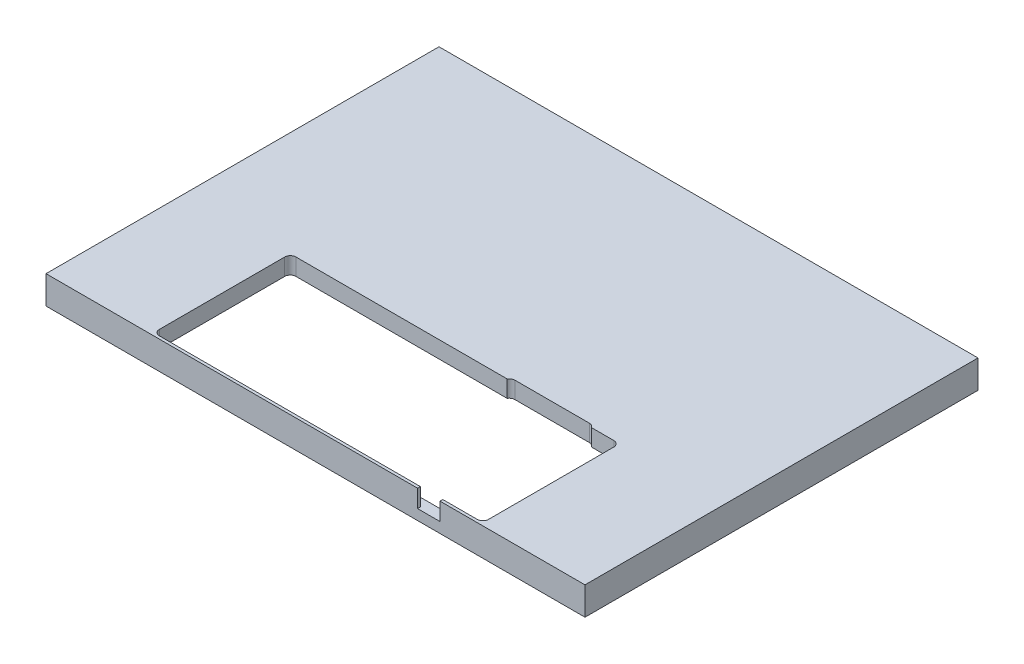
SolidWorks part; units mm, degrees
ref_plane "Front Plane" through (0, 0, 0) normal (0, 0, 1) x (1, 0, 0)
ref_plane "Top Plane" through (0, 0, 0) normal (0, 1, 0) x (1, 0, 0)
ref_plane "Right Plane" through (0, 0, 0) normal (1, 0, 0) x (0, 0, -1)
sketch "Sketch1" plane through (0, 0, 0) normal (0, 1, 0) x (1, 0, 0)
  line L0 (5.08, 5.08) -> (238.76, 5.08)
  line L1 (0, 0) -> (243.84, 0)
  line L2 (0, 0) -> (0, 177.8)
  line L3 (0, 177.8) -> (243.84, 177.8)
  line L4 (243.84, 0) -> (243.84, 177.8)
  line L5 (238.76, 5.08) -> (238.76, 172.72)
  line L6 (5.08, 172.72) -> (238.76, 172.72)
  line L7 (5.08, 5.08) -> (5.08, 172.72)
  dimension "D1" = 177.8
  dimension "D2" = 243.84
  dimension "D3" = 5.08
extrude "Boss-Extrude7" add sketch "Sketch1" along normal blind 12.7
sketch "Sketch6" plane through (0, 12.7, 0) normal (0, 1, 0) x (1, 0, 0)
  line L0 (5.08, 172.72) -> (5.08, 5.08)
  line L1 (5.08, 5.08) -> (238.76, 5.08)
  line L2 (238.76, 5.08) -> (238.76, 172.72)
  line L3 (238.76, 172.72) -> (5.08, 172.72)
extrude "Boss-Extrude8" add sketch "Sketch6" against normal blind 7.62
sketch "Sketch7" plane through (0, 12.7, 0) normal (0, 1, 0) x (1, 0, 0)
  line L0 (0, 0) -> (243.84, 0) construction
  line L1 (0, 177.8) -> (0, 0) construction
  line L2 (243.84, 0) -> (243.84, 177.8) construction
  line L3 (196.37, 1.27) -> (178.2581, 1.27)
  line L4 (47.47, 1.27) -> (47.47, 63.07)
  line L6 (196.37, 63.07) -> (196.37, 1.27)
  line L8 (47.47, 32.17) -> (0, 32.17) construction
  line L9 (196.37, 32.17) -> (243.84, 32.17) construction
  line L11 (168.0981, 0) -> (178.2581, 0)
  line L12 (178.2581, 0) -> (178.2581, 1.27)
  line L14 (157.9954, 1.27) -> (47.47, 1.27)
  line L15 (157.9954, 1.27) -> (168.0981, 1.27)
  line L16 (168.0981, 1.27) -> (168.0981, 0)
  line L18 (183.67, 64.34) -> (145.57, 64.34)
  line L20 (196.37, 63.07) -> (183.67, 63.07)
  line L21 (145.57, 63.07) -> (47.47, 63.07)
  line L22 (183.67, 63.07) -> (183.67, 64.34)
  line L23 (145.57, 63.07) -> (145.57, 64.34)
  dimension "D1" = 1.27
  dimension "D2" = 148.9
  dimension "D3" = 61.8
  dimension "D4" = 10.16
  dimension "D5" = 38.1
  dimension "D6" = 12.7
  dimension "D7" = 1.27
extrude "Cut-Extrude2" cut sketch "Sketch7" against normal blind 8 contours L4 L21 L23 L18 L22 L20 L6 L3 L12 L11 L16 L15 L14
fillet "Fillet1" radius 2.54 4 edges at (47.47, 8.89, -63.07) (47.47, 8.7, -1.27) (196.37, 8.7, -1.27) (196.37, 8.89, -63.07)
fillet "Fillet2" radius 2.54 2 edges at (145.57, 8.89, -64.34) (183.67, 8.89, -64.34)
sketch "Sketch8" plane through (0, 12.7, 0) normal (0, 1, 0) x (1, 0, 0)
  line L0 (50.5293, 86.591) -> (50.5293, 97.9956)
  line L1 (50.5293, 97.9956) -> (62.5181, 97.9956)
  line L2 (62.5181, 97.9956) -> (62.5181, 86.591)
  line L3 (62.5181, 86.591) -> (50.5293, 86.591)
  line L4 (76.9961, 86.591) -> (65.0073, 86.591)
  line L5 (65.0073, 86.591) -> (65.0073, 97.9956)
  line L6 (65.0073, 97.9956) -> (76.9961, 97.9956)
  line L7 (76.9961, 97.9956) -> (76.9961, 86.591)
  line L8 (91.4741, 86.591) -> (79.4853, 86.591)
  line L9 (79.4853, 86.591) -> (79.4853, 97.9956)
  line L10 (79.4853, 97.9956) -> (91.4741, 97.9956)
  line L11 (91.4741, 97.9956) -> (91.4741, 86.591)
  line L12 (105.9521, 86.591) -> (93.9633, 86.591)
  line L13 (93.9633, 86.591) -> (93.9633, 97.9956)
  line L14 (93.9633, 97.9956) -> (105.9521, 97.9956)
  line L15 (105.9521, 97.9956) -> (105.9521, 86.591)
  line L16 (120.4301, 86.591) -> (108.4413, 86.591)
  line L17 (108.4413, 86.591) -> (108.4413, 97.9956)
  line L18 (108.4413, 97.9956) -> (120.4301, 97.9956)
  line L19 (120.4301, 97.9956) -> (120.4301, 86.591)
  line L20 (134.9081, 86.591) -> (122.9193, 86.591)
  line L21 (122.9193, 86.591) -> (122.9193, 97.9956)
  line L22 (122.9193, 97.9956) -> (134.9081, 97.9956)
  line L23 (134.9081, 97.9956) -> (134.9081, 86.591)
  line L24 (149.3861, 86.591) -> (137.3973, 86.591)
  line L25 (137.3973, 86.591) -> (137.3973, 97.9956)
  line L26 (137.3973, 97.9956) -> (149.3861, 97.9956)
  line L27 (149.3861, 97.9956) -> (149.3861, 86.591)
  line L28 (163.8641, 86.591) -> (151.8753, 86.591)
  line L29 (151.8753, 86.591) -> (151.8753, 97.9956)
  line L30 (151.8753, 97.9956) -> (163.8641, 97.9956)
  line L31 (163.8641, 97.9956) -> (163.8641, 86.591)
  line L32 (178.3421, 86.591) -> (166.3533, 86.591)
  line L33 (166.3533, 86.591) -> (166.3533, 97.9956)
  line L34 (166.3533, 97.9956) -> (178.3421, 97.9956)
  line L35 (178.3421, 97.9956) -> (178.3421, 86.591)
  line L36 (192.8201, 86.591) -> (180.8313, 86.591)
  line L37 (180.8313, 86.591) -> (180.8313, 97.9956)
  line L38 (180.8313, 97.9956) -> (192.8201, 97.9956)
  line L39 (192.8201, 97.9956) -> (192.8201, 86.591)
  line L40 (120.4301, 92.2933) -> (122.9193, 92.2933) construction
  line L43 (120.4301, 92.2933) -> (0, 92.2933) construction
  line L44 (0, 177.8) -> (0, 0) construction
  line L45 (47.9893, 86.591) -> (22.5893, 86.591)
  line L46 (22.5893, 86.591) -> (22.5893, 97.9956)
  line L47 (22.5893, 97.9956) -> (47.9893, 97.9956)
  line L48 (47.9893, 97.9956) -> (47.9893, 86.591)
  line L55 (195.3601, 97.9956) -> (195.3601, 86.591)
  line L56 (195.3601, 86.591) -> (233.4601, 86.591)
  line L57 (233.4601, 86.591) -> (233.4601, 97.9956)
  line L58 (233.4601, 97.9956) -> (195.3601, 97.9956)
  line L59 (192.8201, 86.591) -> (195.3601, 86.591) construction
  line L60 (192.8201, 97.9956) -> (195.3601, 97.9956) construction
  line L61 (75.1673, 72.621) -> (75.1673, 84.051)
  line L62 (75.1673, 84.051) -> (174.2273, 84.051)
  line L63 (174.2273, 84.051) -> (174.2273, 72.621)
  line L64 (174.2273, 72.621) -> (75.1673, 72.621)
  line L65 (72.6273, 72.621) -> (72.6273, 84.051)
  line L66 (72.6273, 84.051) -> (56.1173, 84.051)
  line L67 (56.1173, 84.051) -> (56.1173, 72.621)
  line L68 (56.1173, 72.621) -> (72.6273, 72.621)
  line L69 (53.5773, 72.621) -> (53.5773, 84.051)
  line L70 (53.5773, 84.051) -> (41.6393, 84.051)
  line L71 (41.6393, 84.051) -> (41.6393, 72.621)
  line L72 (41.6393, 72.621) -> (53.5773, 72.621)
  line L73 (39.0993, 72.621) -> (39.0993, 84.051)
  line L74 (39.0993, 84.051) -> (22.5893, 84.051)
  line L75 (22.5893, 84.051) -> (22.5893, 72.621)
  line L76 (22.5893, 72.621) -> (39.0993, 72.621)
  line L78 (188.7053, 72.621) -> (188.7053, 84.051)
  line L79 (188.7053, 84.051) -> (176.7673, 84.051)
  line L80 (176.7673, 84.051) -> (176.7673, 72.621)
  line L81 (176.7673, 72.621) -> (188.7053, 72.621)
  line L96 (43.2268, 111.9656) -> (43.2268, 100.5356)
  line L97 (43.2268, 100.5356) -> (55.1648, 100.5356)
  line L98 (55.1648, 100.5356) -> (55.1648, 111.9656)
  line L99 (55.1648, 111.9656) -> (43.2268, 111.9656)
  line L100 (69.5588, 111.9656) -> (57.6208, 111.9656)
  line L101 (57.6208, 111.9656) -> (57.6208, 100.5356)
  line L102 (57.6208, 100.5356) -> (69.5588, 100.5356)
  line L103 (69.5588, 100.5356) -> (69.5588, 111.9656)
  line L104 (83.9528, 111.9656) -> (72.0148, 111.9656)
  line L105 (72.0148, 111.9656) -> (72.0148, 100.5356)
  line L106 (72.0148, 100.5356) -> (83.9528, 100.5356)
  line L107 (83.9528, 100.5356) -> (83.9528, 111.9656)
  line L108 (98.3469, 111.9656) -> (86.4089, 111.9656)
  line L109 (86.4089, 111.9656) -> (86.4089, 100.5356)
  line L110 (86.4089, 100.5356) -> (98.3469, 100.5356)
  line L111 (98.3469, 100.5356) -> (98.3469, 111.9656)
  line L112 (112.7409, 111.9656) -> (100.8029, 111.9656)
  line L113 (100.8029, 111.9656) -> (100.8029, 100.5356)
  line L114 (100.8029, 100.5356) -> (112.7409, 100.5356)
  line L115 (112.7409, 100.5356) -> (112.7409, 111.9656)
  line L116 (127.1349, 111.9656) -> (115.1969, 111.9656)
  line L117 (115.1969, 111.9656) -> (115.1969, 100.5356)
  line L118 (115.1969, 100.5356) -> (127.1349, 100.5356)
  line L119 (127.1349, 100.5356) -> (127.1349, 111.9656)
  line L120 (141.529, 111.9656) -> (129.591, 111.9656)
  line L121 (129.591, 111.9656) -> (129.591, 100.5356)
  line L122 (129.591, 100.5356) -> (141.529, 100.5356)
  line L123 (141.529, 100.5356) -> (141.529, 111.9656)
  line L124 (155.923, 111.9656) -> (143.985, 111.9656)
  line L125 (143.985, 111.9656) -> (143.985, 100.5356)
  line L126 (143.985, 100.5356) -> (155.923, 100.5356)
  line L127 (155.923, 100.5356) -> (155.923, 111.9656)
  line L128 (170.317, 111.9656) -> (158.379, 111.9656)
  line L129 (158.379, 111.9656) -> (158.379, 100.5356)
  line L130 (158.379, 100.5356) -> (170.317, 100.5356)
  line L131 (170.317, 100.5356) -> (170.317, 111.9656)
  line L132 (184.7111, 111.9656) -> (172.7731, 111.9656)
  line L133 (172.7731, 111.9656) -> (172.7731, 100.5356)
  line L134 (172.7731, 100.5356) -> (184.7111, 100.5356)
  line L135 (184.7111, 100.5356) -> (184.7111, 111.9656)
  line L136 (199.1051, 111.9656) -> (187.1671, 111.9656)
  line L137 (187.1671, 111.9656) -> (187.1671, 100.5356)
  line L138 (187.1671, 100.5356) -> (199.1051, 100.5356)
  line L139 (199.1051, 100.5356) -> (199.1051, 111.9656)
  line L140 (40.6868, 100.5356) -> (22.5893, 100.5356)
  line L141 (22.5893, 100.5356) -> (22.5893, 111.9656)
  line L142 (22.5893, 111.9656) -> (40.6868, 111.9656)
  line L143 (40.6868, 111.9656) -> (40.6868, 100.5356)
  line L144 (201.6451, 111.9656) -> (201.6451, 100.5356)
  line L145 (201.6451, 100.5356) -> (233.4601, 100.5356)
  line L146 (233.4601, 100.5356) -> (233.4601, 111.9656)
  line L147 (233.4601, 111.9656) -> (201.6451, 111.9656)
  line L156 (51.8757, 125.9592) -> (39.9377, 125.9592)
  line L157 (39.9377, 125.9592) -> (39.9377, 114.5056)
  line L158 (39.9377, 114.5056) -> (51.8757, 114.5056)
  line L159 (51.8757, 114.5056) -> (51.8757, 125.9592)
  line L196 (66.3537, 125.9592) -> (54.4157, 125.9592)
  line L197 (54.4157, 125.9592) -> (54.4157, 114.5056)
  line L198 (54.4157, 114.5056) -> (66.3537, 114.5056)
  line L199 (66.3537, 114.5056) -> (66.3537, 125.9592)
  line L200 (80.8317, 125.9592) -> (68.8937, 125.9592)
  line L201 (68.8937, 125.9592) -> (68.8937, 114.5056)
  line L202 (68.8937, 114.5056) -> (80.8317, 114.5056)
  line L203 (80.8317, 114.5056) -> (80.8317, 125.9592)
  line L204 (95.3097, 125.9592) -> (83.3717, 125.9592)
  line L205 (83.3717, 125.9592) -> (83.3717, 114.5056)
  line L206 (83.3717, 114.5056) -> (95.3097, 114.5056)
  line L207 (95.3097, 114.5056) -> (95.3097, 125.9592)
  line L208 (109.7877, 125.9592) -> (97.8497, 125.9592)
  line L209 (97.8497, 125.9592) -> (97.8497, 114.5056)
  line L210 (97.8497, 114.5056) -> (109.7877, 114.5056)
  line L211 (109.7877, 114.5056) -> (109.7877, 125.9592)
  line L212 (124.2657, 125.9592) -> (112.3277, 125.9592)
  line L213 (112.3277, 125.9592) -> (112.3277, 114.5056)
  line L214 (112.3277, 114.5056) -> (124.2657, 114.5056)
  line L215 (124.2657, 114.5056) -> (124.2657, 125.9592)
  line L216 (138.7437, 125.9592) -> (126.8057, 125.9592)
  line L217 (126.8057, 125.9592) -> (126.8057, 114.5056)
  line L218 (126.8057, 114.5056) -> (138.7437, 114.5056)
  line L219 (138.7437, 114.5056) -> (138.7437, 125.9592)
  line L220 (153.2217, 125.9592) -> (141.2837, 125.9592)
  line L221 (141.2837, 125.9592) -> (141.2837, 114.5056)
  line L222 (141.2837, 114.5056) -> (153.2217, 114.5056)
  line L223 (153.2217, 114.5056) -> (153.2217, 125.9592)
  line L224 (167.6997, 125.9592) -> (155.7617, 125.9592)
  line L225 (155.7617, 125.9592) -> (155.7617, 114.5056)
  line L226 (155.7617, 114.5056) -> (167.6997, 114.5056)
  line L227 (167.6997, 114.5056) -> (167.6997, 125.9592)
  line L228 (182.1777, 125.9592) -> (170.2397, 125.9592)
  line L229 (170.2397, 125.9592) -> (170.2397, 114.5056)
  line L230 (170.2397, 114.5056) -> (182.1777, 114.5056)
  line L231 (182.1777, 114.5056) -> (182.1777, 125.9592)
  line L232 (196.6557, 125.9592) -> (184.7177, 125.9592)
  line L233 (184.7177, 125.9592) -> (184.7177, 114.5056)
  line L234 (184.7177, 114.5056) -> (196.6557, 114.5056)
  line L235 (196.6557, 114.5056) -> (196.6557, 125.9592)
  line L236 (211.1337, 125.9592) -> (199.1957, 125.9592)
  line L237 (199.1957, 125.9592) -> (199.1957, 114.5056)
  line L238 (199.1957, 114.5056) -> (211.1337, 114.5056)
  line L239 (211.1337, 114.5056) -> (211.1337, 125.9592)
  line L240 (37.3977, 114.5056) -> (22.5893, 114.5056)
  line L241 (22.5893, 114.5056) -> (22.5893, 125.9592)
  line L242 (22.5893, 125.9592) -> (37.3977, 125.9592)
  line L243 (37.3977, 125.9592) -> (37.3977, 114.5056)
  line L244 (212.9454, 113.6508) -> (212.9454, 125.9592)
  line L245 (212.9454, 125.9592) -> (233.4601, 125.9592)
  line L246 (233.4601, 125.9592) -> (233.4601, 113.6508)
  line L247 (233.4601, 113.6508) -> (212.9454, 113.6508)
  line L248 (22.5893, 128.4992) -> (22.5893, 139.9292)
  line L249 (22.5893, 139.9292) -> (34.5273, 139.9292)
  line L250 (34.5273, 139.9292) -> (34.5273, 128.4992)
  line L251 (34.5273, 128.4992) -> (22.5893, 128.4992)
  line L252 (49.0053, 128.4992) -> (37.0673, 128.4992)
  line L253 (37.0673, 128.4992) -> (37.0673, 139.9292)
  line L254 (37.0673, 139.9292) -> (49.0053, 139.9292)
  line L255 (49.0053, 139.9292) -> (49.0053, 128.4992)
  line L256 (63.4833, 128.4992) -> (51.5453, 128.4992)
  line L257 (51.5453, 128.4992) -> (51.5453, 139.9292)
  line L258 (51.5453, 139.9292) -> (63.4833, 139.9292)
  line L259 (63.4833, 139.9292) -> (63.4833, 128.4992)
  line L260 (77.9613, 128.4992) -> (66.0233, 128.4992)
  line L261 (66.0233, 128.4992) -> (66.0233, 139.9292)
  line L262 (66.0233, 139.9292) -> (77.9613, 139.9292)
  line L263 (77.9613, 139.9292) -> (77.9613, 128.4992)
  line L264 (92.4393, 128.4992) -> (80.5013, 128.4992)
  line L265 (80.5013, 128.4992) -> (80.5013, 139.9292)
  line L266 (80.5013, 139.9292) -> (92.4393, 139.9292)
  line L267 (92.4393, 139.9292) -> (92.4393, 128.4992)
  line L268 (106.9173, 128.4992) -> (94.9793, 128.4992)
  line L269 (94.9793, 128.4992) -> (94.9793, 139.9292)
  line L270 (94.9793, 139.9292) -> (106.9173, 139.9292)
  line L271 (106.9173, 139.9292) -> (106.9173, 128.4992)
  line L272 (121.3953, 128.4992) -> (109.4573, 128.4992)
  line L273 (109.4573, 128.4992) -> (109.4573, 139.9292)
  line L274 (109.4573, 139.9292) -> (121.3953, 139.9292)
  line L275 (121.3953, 139.9292) -> (121.3953, 128.4992)
  line L276 (135.8733, 128.4992) -> (123.9353, 128.4992)
  line L277 (123.9353, 128.4992) -> (123.9353, 139.9292)
  line L278 (123.9353, 139.9292) -> (135.8733, 139.9292)
  line L279 (135.8733, 139.9292) -> (135.8733, 128.4992)
  line L280 (150.3513, 128.4992) -> (138.4133, 128.4992)
  line L281 (138.4133, 128.4992) -> (138.4133, 139.9292)
  line L282 (138.4133, 139.9292) -> (150.3513, 139.9292)
  line L283 (150.3513, 139.9292) -> (150.3513, 128.4992)
  line L284 (164.8293, 128.4992) -> (152.8913, 128.4992)
  line L285 (152.8913, 128.4992) -> (152.8913, 139.9292)
  line L286 (152.8913, 139.9292) -> (164.8293, 139.9292)
  line L287 (164.8293, 139.9292) -> (164.8293, 128.4992)
  line L288 (179.3073, 128.4992) -> (167.3693, 128.4992)
  line L289 (167.3693, 128.4992) -> (167.3693, 139.9292)
  line L290 (167.3693, 139.9292) -> (179.3073, 139.9292)
  line L291 (179.3073, 139.9292) -> (179.3073, 128.4992)
  line L292 (193.7853, 128.4992) -> (181.8473, 128.4992)
  line L293 (181.8473, 128.4992) -> (181.8473, 139.9292)
  line L294 (181.8473, 139.9292) -> (193.7853, 139.9292)
  line L295 (193.7853, 139.9292) -> (193.7853, 128.4992)
  line L296 (208.2633, 128.4992) -> (196.3253, 128.4992)
  line L297 (196.3253, 128.4992) -> (196.3253, 139.9292)
  line L298 (196.3253, 139.9292) -> (208.2633, 139.9292)
  line L299 (208.2633, 139.9292) -> (208.2633, 128.4992)
  line L300 (210.8033, 128.4992) -> (233.4601, 128.4992)
  line L301 (233.4601, 128.4992) -> (233.4601, 139.9292)
  line L302 (233.4601, 139.9292) -> (210.8033, 139.9292)
  line L303 (210.8033, 139.9292) -> (210.8033, 128.4992)
  line L304 (221.5221, 72.621) -> (221.5221, 84.0664)
  line L305 (221.5221, 84.0664) -> (233.4601, 84.0664)
  line L306 (233.4601, 84.0664) -> (233.4601, 72.621)
  line L307 (233.4601, 72.621) -> (221.5221, 72.621)
  line L308 (191.2453, 72.621) -> (191.2453, 84.051)
  line L309 (191.2453, 84.051) -> (203.1833, 84.051)
  line L310 (203.1833, 84.051) -> (203.1833, 72.621)
  line L311 (203.1833, 72.621) -> (191.2453, 72.621)
  line L318 (205.7233, 84.051) -> (205.7233, 72.621)
  line L319 (205.7233, 72.621) -> (220.2767, 72.621)
  line L320 (220.2767, 72.621) -> (220.2767, 84.051)
  line L321 (220.2767, 84.051) -> (205.7233, 84.051)
  dimension "D1" = 11.9888
  dimension "D2" = 11.4046
  dimension "D4" = 25.4
  dimension "D5" = 2.4892
  dimension "D6" = 2.54
  dimension "D7" = 38.1
  dimension "D8" = 2.54
  dimension "D9" = 99.06
  dimension "D10" = 11.43
  dimension "D11" = 11.43
  dimension "D12" = 2.54
  dimension "D13" = 16.51
  dimension "D14" = 11.938
  dimension "D15" = 16.51
  dimension "D16" = 2.54
  dimension "D17" = 2.54
  dimension "D18" = 2.54
  dimension "D19" = 11.938
  dimension "D20" = 11.4454
  dimension "D21" = 11.43
  dimension "D22" = 2.54
  dimension "D23" = 11.938
  dimension "D24" = 11.938
  dimension "D25" = 2.54
  dimension "D26" = 11.43
  dimension "D27" = 1.2454
  dimension "D28" = 11.938
  dimension "D29" = 11.43
  dimension "D30" = 2.54
  dimension "D32" = 2.54
  dimension "D33" = 2.54
  dimension "D34" = 2.54
  dimension "D35" = 12
  dimension "D36" = 2.54
  dimension "D37" = 2.54
  dimension "D38" = 11.938
  dimension "D39" = 11.43
  dimension "D41" = 2.54
  dimension "D42" = 2.54
  dimension "D44" = 2.54
  dimension "D3" = 10
  dimension "D31" = 11
  dimension "D40" = 13
